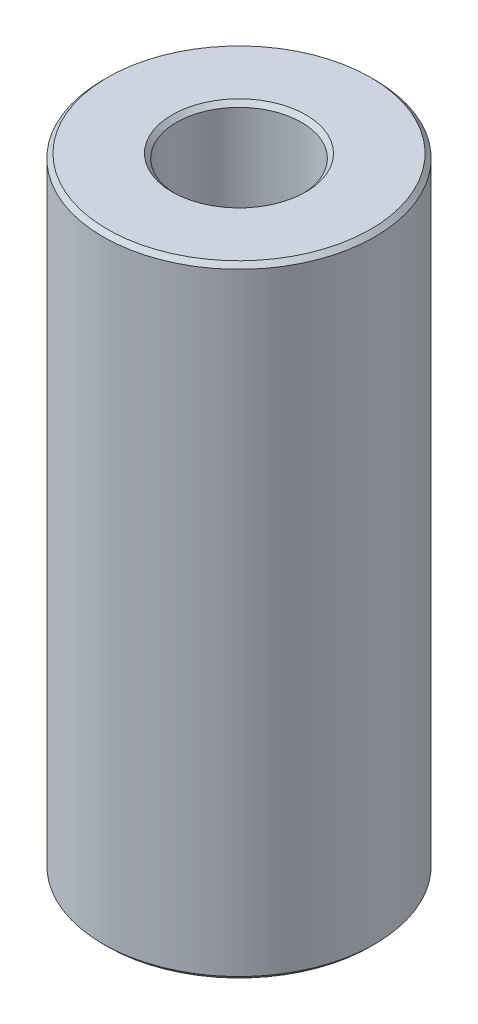
SolidWorks part; units mm, degrees
ref_plane "Front Plane" through (0, 0, 0) normal (0, 0, 1) x (1, 0, 0)
ref_plane "Top Plane" through (0, 0, 0) normal (0, 1, 0) x (1, 0, 0)
ref_plane "Right Plane" through (0, 0, 0) normal (1, 0, 0) x (0, 0, -1)
sketch "Sketch1" plane through (0, 0, 0) normal (0, 1, 0) x (1, 0, 0)
  circle A0 centre (0, 0) radius 47.5
  dimension "SLEEVE_OD" = 95
extrude "Boss-Extrude1" add sketch "Sketch1" along normal blind 217.0775
sketch "Sketch2" plane through (0, 0, 0) normal (0, 1, 0) x (1, 0, 0)
  circle A0 centre (0, 0) radius 21.846
  dimension "BORE_D" = 43.6921
extrude "Cut-Extrude1" cut sketch "Sketch2" along normal through all
chamfer "Chamfer1" distance 1.5178 angle 45 4 edges at (0, 217.0775, 21.846) (0, 0, 21.846) (0, 0, 47.5) (0, 217.0775, 47.5)
